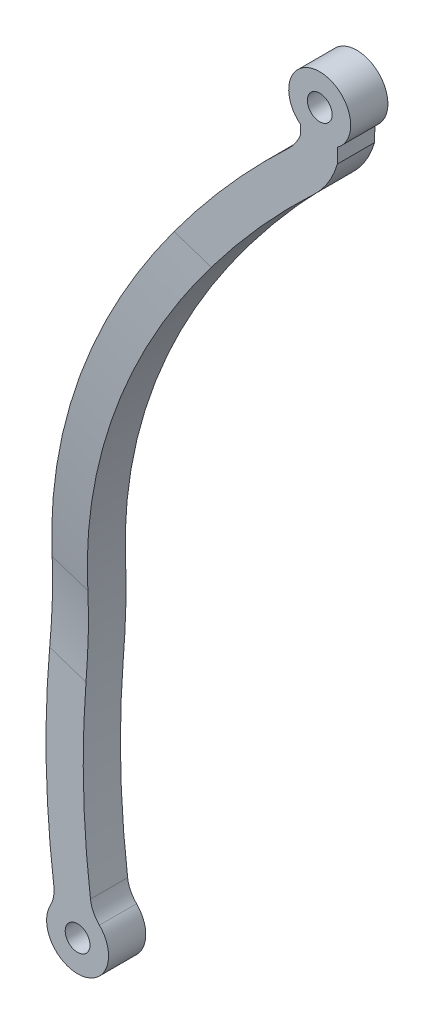
SolidWorks part; units mm, degrees
material "Brass"
ref_plane "Front" through (0, 0, 0) normal (0, 0, 1) x (1, 0, 0)
ref_plane "Top" through (0, 0, 0) normal (0, 1, 0) x (1, 0, 0)
ref_plane "Right" through (0, 0, 0) normal (1, 0, 0) x (0, 0, -1)
sketch "Sketch1" plane through (0, 0, 0) normal (0, 0, 1) x (1, 0, 0)
  line L0 (132.699, 279.3962) -> (36.57, -9.784) construction
  line L2 (125.9358, 259.0509) -> (-62.2753, 321.6158) construction
  line L4 (138.5035, 271.2532) -> (138.3866, 266.4271)
  line L7 (132.699, 279.3962) -> (132.4084, 267.3997) construction
  line L8 (126.507, 271.5439) -> (126.4334, 268.5064)
  circle A0 centre (36.57, -9.784) radius 4
  circle A1 centre (132.699, 279.3962) radius 4
  arc A4 (29.4139, -2.7989) -> (41.2731, -0.959) centre (36.57, -9.784) ccw
  arc A6 (29.4139, -2.7989) -> (122.7844, 263.1037) centre (332.3836, 40.1593) cw
  arc A7 (41.2731, -0.959) -> (131.004, 254.3608) centre (332.3836, 40.1593) cw
  arc A8 (126.8942, 258.7323) -> (36.57, -9.784) centre (332.3836, 40.1593) ccw construction
  arc A12 (138.5035, 271.2532) -> (126.507, 271.5439) centre (132.699, 279.3962) ccw
  arc A13 (126.8942, 258.7323) -> (132.4084, 267.3997) centre (112.6532, 273.8801) ccw construction
  arc A14 (126.4334, 268.5064) -> (122.7844, 263.1037) centre (112.6532, 273.8801) cw
  arc A15 (138.3866, 266.4271) -> (131.004, 254.3608) centre (112.6532, 273.8801) cw
  arc A16 (133.3843, 275.4553) -> (132.699, 279.3962) centre (112.6532, 273.8801) ccw construction
  point P12 (84.635, 134.808)
  dimension "D1" = 36.57
  dimension "D3" = 279.3962
  dimension "D4" = 132.699
  dimension "D5" = 8
  dimension "D6" = 20
  dimension "D7" = 6
  dimension "D8" = 6
  dimension "D12" = 12
  dimension "D9" = 6
  dimension "D11" = 17
  dimension "D10" = 6
  dimension "D13" = 300
  dimension "D2" = 9.784
extrude "Boss-Extrude1" add sketch "Sketch1" against normal blind 30
fillet "Fillet1" radius 10 2 edges at (29.4139, -2.7989, -15) (41.2731, -0.959, -15)
ref_axis "Axis1" through (132.699, 279.3962, -30) along (0, 0, 1)
ref_axis "Axis2" through (36.57, -9.784, -30) along (0, 0, 1)
ref_plane "Plane1" through (35.8598, -11.9205, 0) normal (0.9489, -0.3154, 0) x (0, 0, -1)
sketch "Sketch2" plane through (35.8598, -11.9205, 0) normal (0.9489, -0.3154, 0) x (0, 0, -1)
  line L0 (18, 72.2514) -> (18, -41.651)
  line L1 (18, 72.2514) -> (-39.246, 72.2514) construction
  line L2 (0, 288.4025) -> (0, 10.0773) construction
  line L3 (30, 10.0773) -> (30, 288.4025) construction
  line L4 (12, 328.2307) -> (12, 236.9906)
  line L5 (12, 236.9906) -> (59.1953, 236.9906) construction
  line L6 (0, 326.1043) -> (0, 236.9906)
  line L7 (18, -41.651) -> (-79.9142, -10.5188)
  line L8 (30, -24.9338) -> (30, 72.2514)
  line L9 (26.5805, 103.5473) -> (14.8637, 100.9556)
  line L10 (0, 6.2514) -> (0, -1.7486) construction
  line L11 (0, 6.2514) -> (0, -1.7486)
  line L12 (30, 302.9906) -> (30, 310.9906) construction
  line L13 (30, 302.9906) -> (30, 310.9906)
  line L14 (-79.9142, -10.5188) -> (0, 236.9906)
  line L15 (12, 328.2307) -> (0, 326.1043)
  line L16 (59.1953, 236.9906) -> (59.1953, 72.2514) construction
  line L17 (12, 328.2307) -> (155.7177, 285.4602)
  line L18 (155.7177, 285.4602) -> (30, 72.2514)
  arc A0 (18, 72.2514) -> (14.8637, 100.9556) centre (-114.9209, 72.2514) ccw
  arc A1 (14.8637, 100.9556) -> (0, 236.9906) centre (629.9402, 236.9906) cw
  arc A2 (12, 236.9906) -> (26.5805, 103.5473) centre (629.9402, 236.9906) ccw
  arc A3 (26.5805, 103.5473) -> (30, 72.2514) centre (-114.9209, 72.2514) cw
  point P17 (30, 306.9906)
  point P20 (20.7221, 102.2514)
  point P23 (0, 2.2514)
  dimension "D1" = 12
  dimension "D2" = 12
  dimension "D3" = 70
  dimension "D4" = 70
  dimension "D5" = 100
extrude "Cut-Extrude1" cut sketch "Sketch2" against normal mid plane 100 contours A2 A3 L18 L17 L4 | A0 A1 L14 L7 L0 region at (55.1183, 46.014, 18.8617) region at (107.4932, 203.5707, -63.0635)
